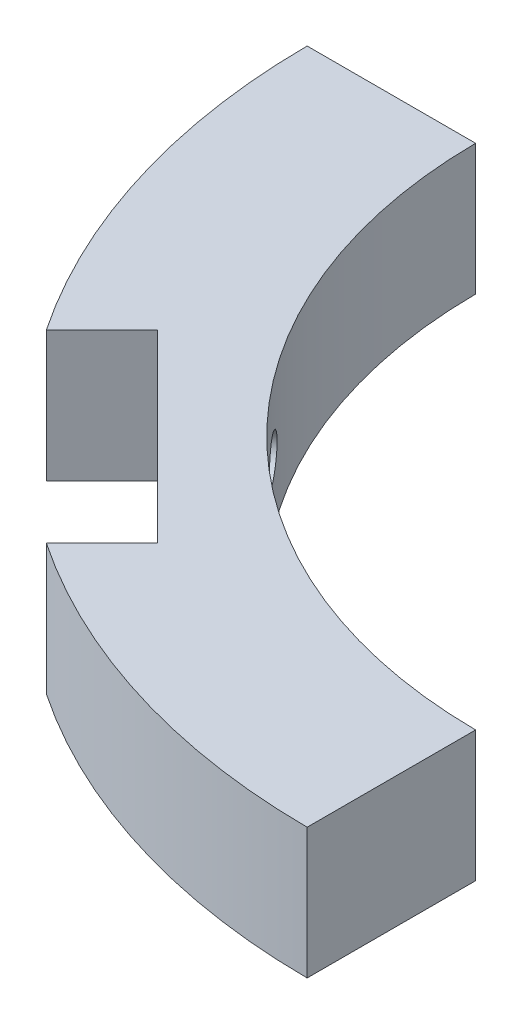
SolidWorks part; units mm, degrees
material "6061-T6 (SS)"
ref_plane "Front Plane" through (0, 0, 0) normal (0, 0, 1) x (1, 0, 0)
ref_plane "Top Plane" through (0, 0, 0) normal (0, 1, 0) x (1, 0, 0)
ref_plane "Right Plane" through (0, 0, 0) normal (1, 0, 0) x (0, 0, -1)
sketch "Sketch1" plane through (0, 0, 0) normal (0, 1, 0) x (1, 0, 0)
  line L0 (0, 0) -> (-24.5, 0) construction
  line L1 (0, 0) -> (0, -24.5) construction
  line L2 (-19.5497, -0.1) -> (-25.9998, -0.1)
  line L3 (-0.1, -19.5497) -> (-0.1, -25.9998)
  line L4 (-0.1, -0.1) -> (-24.5, -0.1) construction
  line L5 (-0.1, -0.1) -> (-0.1, -24.5) construction
  arc A0 (-19.5497, -0.1) -> (-0.1, -19.5497) centre (0, 0) ccw
  arc A1 (-25.9998, -0.1) -> (-0.1, -25.9998) centre (0, 0) ccw
  dimension "D1" = 39.1
  dimension "D2" = 52
  dimension "D3" = 0.1
extrude "Boss-Extrude1" add sketch "Sketch1" along normal mid plane 5
sketch "Sketch2" plane through (0, 2.5, 0) normal (0, 1, 0) x (1, 0, 0)
  line L0 (-18.3848, -18.3848) -> (0, 0) construction
  line L1 (-21.9203, -14.8492) -> (-14.8492, -21.9203)
  line L5 (-21.9203, -14.8492) -> (-19.4454, -12.3744)
  line L6 (-19.4454, -12.3744) -> (-12.3744, -19.4454)
  line L7 (-12.3744, -19.4454) -> (-14.8492, -21.9203)
  arc A0 (-25.9998, -0.1) -> (-0.1, -25.9998) centre (0, 0) ccw construction
  point P9 (-18.3848, -18.3848)
  dimension "D1" = 3.5
  dimension "D2" = 10
extrude "Cut-Extrude1" cut sketch "Sketch2" against normal through all
sketch "Sketch3" plane through (-15.9099, 0, 15.9099) normal (-0.7071, 0, 0.7071) x (0.7071, 0, 0.7071)
  line L0 (-5, 0) -> (5, 0) construction
  line L1 (-5, -2.5) -> (-5, 2.5) construction
  line L2 (5, 2.5) -> (5, -2.5) construction
  line L3 (0, 0) -> (0, 2.5) construction
  line L4 (5, 2.5) -> (-5, 2.5) construction
  point P6 (-2.5, 0)
  point P12 (2.5, 0)
  dimension "D1" = 2.5
hole_wizard "Tap Drill for M2x0.4 Tap1" positions "3DSketch1" profile "Sketch4" hole size "M2x0.4" standard "ANSI Metric" end condition through all
sketch3d "3DSketch1"
  point P0 (-17.6777, 0, 14.1421)
  point P3 (-14.1421, 0, 17.6777)
sketch "Sketch4" plane through (-17.6777, 0, 14.1421) normal (0, 1, 0) x (0.7071, 0, 0.7071)
  line L0 (0, 0) -> (0, 22.3586)
  line L1 (0, 22.3586) -> (0.8, 22.3586)
  line L2 (0.8, 22.3586) -> (0.8, 0)
  line L5 (0.8, 0) -> (0, 0)
  line L11 (0, -6.35) -> (0, 107.95) construction
  dimension "Thru Hole Dia." = 1.6
  dimension "Thru Hole Depth" = 22.3586
thread "Thread1" pitch 0.4 method extrude profile "Thread Profile1" start angle 0, offset 0, length 0.8, pitch 0.4, diameter 1.6
ref_plane "Plane1" through (-18.2434, 0, 13.5765) normal (0, -1, 0) x (-0.7071, 0, -0.7071)
sketch "Thread Profile1" plane through (-18.2434, 0, 13.5765) normal (0, -1, 0) x (-0.7071, 0, -0.7071)
  line L0 (0, 0) -> (0, 0.4) construction
  line L11 (0, 0) -> (0, 0.35)
  line L12 (0, 0.35) -> (-0.2165, 0.225)
  line L13 (-0.2165, 0.225) -> (-0.2165, 0.125)
  line L15 (-0.2165, 0.125) -> (0, 0)
  line L17 (-0.2165, 0.175) -> (0, 0.175) construction
  point P2 (0, 0)
  dimension "Pitch" = 0.4
  dimension "Profile_Angle" = 60
  dimension "Profile_Land" = 0.1
  dimension "Profile_Height" = 0.2165
thread "Thread2" pitch 0.4 method extrude profile "Thread Profile2" start angle 0, offset 0, length 0.8, pitch 0.4, diameter 1.6
ref_plane "Plane2" through (-14.7078, 0, 17.112) normal (0, -1, 0) x (-0.7071, 0, -0.7071)
sketch "Thread Profile2" plane through (-14.7078, 0, 17.112) normal (0, -1, 0) x (-0.7071, 0, -0.7071)
  line L0 (0, 0) -> (0, 0.4) construction
  line L11 (0, 0) -> (0, 0.35)
  line L12 (0, 0.35) -> (-0.2165, 0.225)
  line L13 (-0.2165, 0.225) -> (-0.2165, 0.125)
  line L15 (-0.2165, 0.125) -> (0, 0)
  line L17 (-0.2165, 0.175) -> (0, 0.175) construction
  point P2 (0, 0)
  dimension "Pitch" = 0.4
  dimension "Profile_Angle" = 60
  dimension "Profile_Land" = 0.1
  dimension "Profile_Height" = 0.2165
